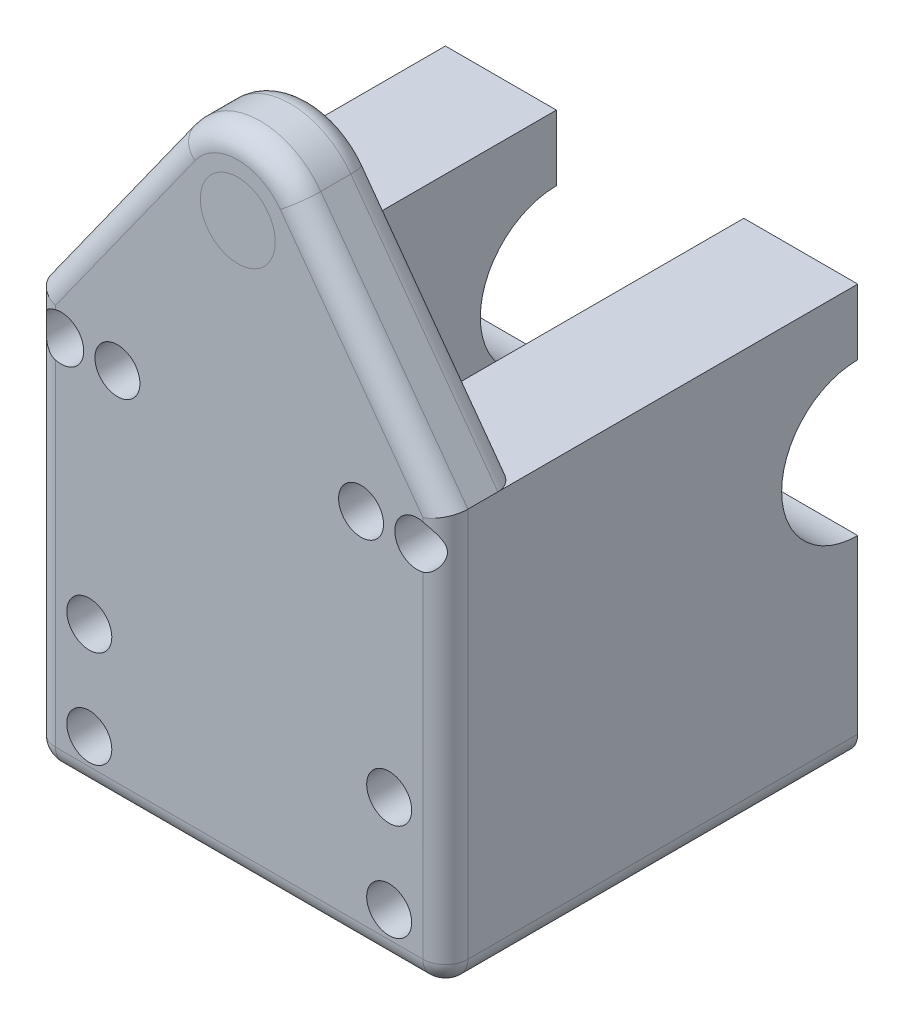
SolidWorks part; units mm, degrees
ref_plane "Front Plane" through (0, 0, 0) normal (1, 0, 0) x (0, 1, 0)
ref_plane "Top Plane" through (0, 0, 0) normal (0, 0, 1) x (0, 1, 0)
ref_plane "Right Plane" through (0, 0, 0) normal (0, 1, 0) x (-1, 0, 0)
sketch "Sketch1" plane through (0, 0, 0) normal (0, 0, 1) x (0, 1, 0)
  line L1 (-27.5, 27.3037) -> (27.5, 27.3037)
  line L2 (-27.5, 27.3037) -> (-27.5, -27.6963)
  line L3 (-27.5, -27.6963) -> (27.5, -27.6963)
  line L4 (27.5, 27.3037) -> (27.5, -27.6963)
  line L5 (-27.5, 12.5) -> (27.5, 12.5)
  line L6 (-27.5, 12.5) -> (-27.5, -12.5)
  line L7 (-27.5, -12.5) -> (27.5, -12.5)
  line L8 (27.5, 12.5) -> (27.5, -12.5)
  point P0 (0, 0)
  point P6 (0, 0)
  dimension "D1" = 55
  dimension "D2" = 55
  dimension "D3" = 25
extrude "Boss-Extrude1" add sketch "Sketch1" along normal blind 45 contours L2 L5 L4 L1 | L7 L2 L3 L4
sketch "Sketch2" plane through (0, 0, 45) normal (0, 0, 1) x (1, 0, 0)
  line L1 (-27.3037, 27.5) -> (27.6963, 27.5)
  line L2 (-27.3037, 27.5) -> (-27.3037, -27.5)
  line L3 (-27.3037, -27.5) -> (27.6963, -27.5)
  line L4 (27.6963, 27.5) -> (27.6963, -27.5)
extrude "Boss-Extrude2" add sketch "Sketch2" along normal blind 10
sketch "Sketch3" plane through (0, 0, 55) normal (0, 0, 1) x (1, 0, 0)
  line L0 (0, 48.5) -> (0.1963, 27.5) construction
  line L1 (27.6963, 27.5) -> (-27.3037, 27.5) construction
  line L2 (-27.3037, 27.5) -> (-8.1352, 54.3153)
  line L3 (27.6963, 27.5) -> (8.079, 54.3932)
  line L4 (-27.3037, 27.5) -> (27.6963, 27.5)
  circle A0 centre (0, 48.5) radius 5
  circle A1 centre (0, 48.5) radius 10
  dimension "D1" = 10
  dimension "D2" = 21
  dimension "D3" = 5
extrude "Boss-Extrude3" add sketch "Sketch3" against normal blind 10
sketch "Sketch4" plane through (0, 0, 55) normal (0, 0, 1) x (1, 0, 0)
  circle A0 centre (0, 48.5) radius 5
extrude "Boss-Extrude4" add sketch "Sketch4" against normal blind 3 separate body
sketch "Sketch5" plane through (27.6963, 0, 0) normal (1, 0, 0) x (0, 1, 0)
  line L0 (27.5, 0) -> (8.6, 0) construction
  line L1 (-27.5, 0) -> (27.5, 0) construction
  circle A0 centre (8.6, 0) radius 10.15
  dimension "D2" = 20.3
  dimension "D1" = 18.9
extrude "Cut-Extrude1" cut sketch "Sketch5" against normal blind 51.5
sketch "Sketch8" plane through (0, 0, 0) normal (0, 0, -1) x (1, 0, 0)
  circle A0 centre (20.1963, 21.0125) radius 1.75
  circle A1 centre (20.1963, 8.0375) radius 1.75
  circle A2 centre (23.9463, -23.125) radius 1.75
  circle A3 centre (16.4463, -23.125) radius 1.75
  circle A4 centre (-16.0537, -23.125) radius 1.75
  circle A5 centre (-23.5537, -23.125) radius 1.75
  circle A6 centre (-19.8037, 8.0375) radius 1.75
  circle A7 centre (-19.8037, 21.0125) radius 1.75
  dimension "D1" = 3.5
extrude "Cut-Extrude3" cut sketch "Sketch8" against normal through all
sketch "Sketch9" plane through (0, 0, 55) normal (0, 0, 1) x (1, 0, 0)
  circle A0 centre (23.9463, 23.125) radius 3
  circle A1 centre (16.4463, 23.125) radius 3
  circle A2 centre (20.1963, -8.0375) radius 3
  circle A3 centre (20.1963, -21.0125) radius 3
  circle A4 centre (-16.0537, 23.125) radius 3
  circle A5 centre (-23.5537, 23.125) radius 3
  circle A6 centre (-19.8037, -8.0375) radius 3
  circle A7 centre (-19.8037, -21.0125) radius 3
  dimension "D1" = 6
extrude "Cut-Extrude4" cut sketch "Sketch9" against normal blind 40
fillet "Fillet2" radius 3 12 edges at (17.8876, 40.9466, 55) (17.8876, 40.9466, 45) (-17.7195, 40.9077, 45) (-17.7195, 40.9077, 55) (5, 48.5, 45) (-0.048, 58.4999, 55) (-0.048, 58.4999, 45) (27.6963, 0, 55) (0.1963, -27.5, 55) (-27.3037, 0, 55) (27.6963, -27.5, 27.5) (-27.3037, -27.5, 27.5)
